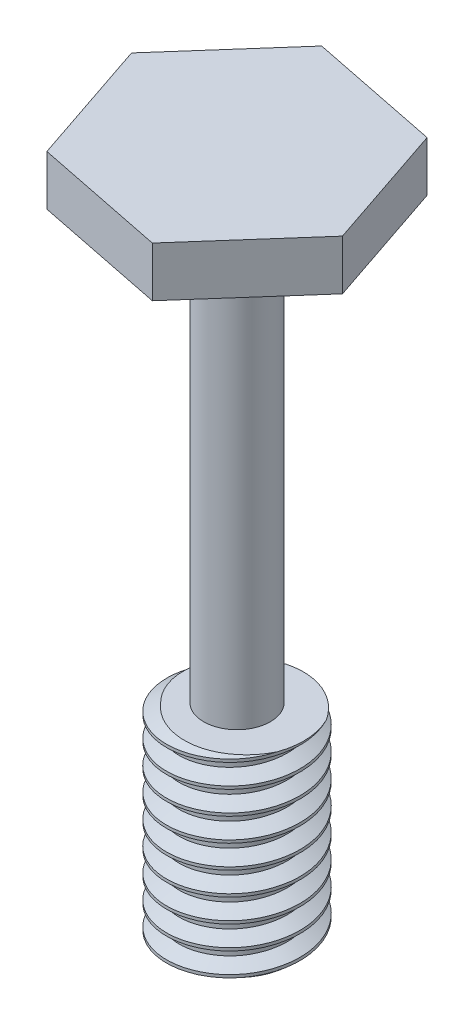
SolidWorks part; units mm, degrees
ref_plane "Front Plane" through (0, 0, 0) normal (0, 0, 1) x (1, 0, 0)
ref_plane "Top Plane" through (0, 0, 0) normal (0, 1, 0) x (1, 0, 0)
ref_plane "Right Plane" through (0, 0, 0) normal (1, 0, 0) x (0, 0, -1)
sketch "Sketch1" plane through (0, 0, 0) normal (0, 0, 1) x (1, 0, 0)
  line L0 (0, 9.1733) -> (0, -16.4086) construction
  line L1 (0, 20.5) -> (4, 20.5)
  line L2 (4, 20.5) -> (4, 19)
  line L3 (4, 19) -> (1, 19)
  line L4 (1, 19) -> (1, 6)
  line L5 (1, 6) -> (2, 6)
  line L6 (2, 6) -> (2, 0)
  line L7 (2, 0) -> (0, 0)
  line L8 (0, 0) -> (0, 20.5)
  dimension "D1" = 20.5
  dimension "D2" = 4
  dimension "D3" = 13
  dimension "D4" = 6
  dimension "D5" = 2
  dimension "D6" = 3
revolve "Revolve1" add sketch "Sketch1" angle 360 about L0
thread "Thread1" pitch 0.7 method cut profile "Thread Profile1" start angle 0, offset 1, length 0, pitch 0.7, diameter 4
ref_plane "Plane1" through (-2, 7, 0) normal (0, 0, 1) x (-1, 0, 0)
sketch "Thread Profile1" plane through (-2, 7, 0) normal (0, 0, 1) x (-1, 0, 0)
  line L0 (0, 0) -> (0, 0.7) construction
  line L11 (0, 0) -> (0, 0.6125)
  line L12 (0, 0.6125) -> (-0.3789, 0.3937)
  line L13 (-0.3789, 0.3937) -> (-0.3789, 0.2187)
  line L15 (-0.3789, 0.2187) -> (0, 0)
  line L17 (-0.3789, 0.3062) -> (0, 0.3062) construction
  point P2 (0, 0)
  dimension "Pitch" = 0.7
  dimension "Profile_Angle" = 60
  dimension "Profile_Land" = 0.175
  dimension "Profile_Height" = 0.3789
sketch "Sketch2" plane through (0, 20.5, 0) normal (0, 1, 0) x (1, 0, 0)
  circle A0 centre (0, 0) radius 4
extrude "Cut-Extrude1" cut sketch "Sketch2" against normal blind 1.5
sketch "Sketch3" plane through (0, 19, 0) normal (0, 1, 0) x (1, 0, 0)
  line L1 (-2.6717, -3.0323) -> (1.2902, -3.83)
  line L2 (1.2902, -3.83) -> (3.962, -0.7976)
  line L3 (3.962, -0.7976) -> (2.6717, 3.0323)
  line L4 (2.6717, 3.0323) -> (-1.2902, 3.83)
  line L5 (-1.2902, 3.83) -> (-3.962, 0.7976)
  line L6 (-3.962, 0.7976) -> (-2.6717, -3.0323)
  circle A0 centre (0, 0) radius 3.5 construction
  dimension "D1" = 7
extrude "Boss-Extrude1" add sketch "Sketch3" along normal blind 1.5
